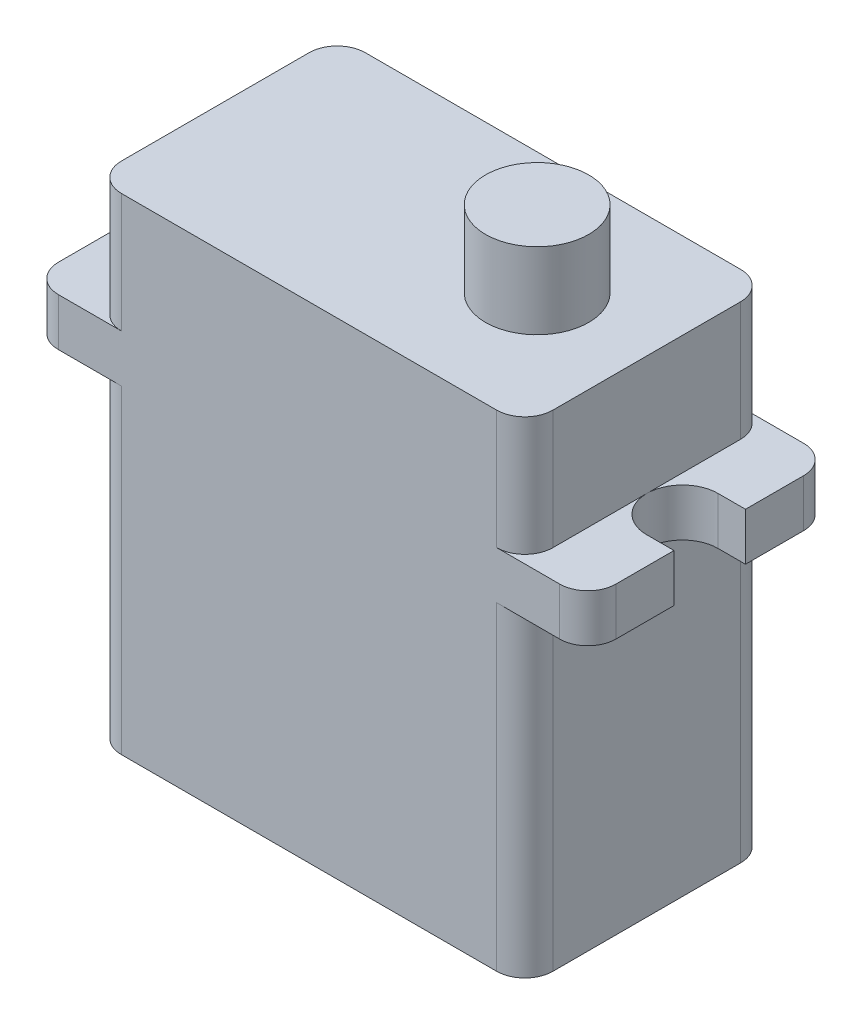
SolidWorks part; units mm, degrees
ref_plane "Front Plane" through (0, 0, 0) normal (0, 0, 1) x (1, 0, 0)
ref_plane "Top Plane" through (0, 0, 0) normal (0, 1, 0) x (1, 0, 0)
ref_plane "Right Plane" through (0, 0, 0) normal (1, 0, 0) x (0, 0, -1)
sketch "Sketch2" plane through (0, 0, 0) normal (0, 1, 0) x (1, 0, 0)
  line L1 (1.5, 0) -> (21.5, 0)
  line L2 (0, -1.5) -> (0, -11.5)
  line L3 (1.5, -13) -> (21.5, -13)
  line L4 (23, -1.5) -> (23, -11.5)
  arc A0 (21.5, -13) -> (23, -11.5) centre (21.5, -11.5) ccw
  arc A1 (1.5, -13) -> (0, -11.5) centre (1.5, -11.5) cw
  arc A2 (0, -1.5) -> (1.5, 0) centre (1.5, -1.5) cw
  arc A3 (23, -1.5) -> (21.5, 0) centre (21.5, -1.5) ccw
  point P7 (23, -13)
  point P12 (0, 0)
  point P15 (23, 0)
  dimension "D3" = 1.5
  dimension "D1" = 23
  dimension "D2" = 13
extrude "Boss-Extrude1" add sketch "Sketch2" along normal blind 17.018 contours L2 A1 L3 A0 L4 A3 L1 A2
sketch "Sketch3" plane through (0, 17.018, 0) normal (0, 1, 0) x (1, 0, 0)
  line L0 (1.5, -13) -> (21.5, -13) construction
  line L1 (-1.859, 0) -> (24.859, 0)
  line L2 (-3.359, -1.5) -> (-3.359, -11.5)
  line L3 (-1.859, -13) -> (24.859, -13)
  line L4 (26.359, -1.5) -> (26.359, -11.5)
  line L5 (1.5, 0) -> (21.5, 0) construction
  line L6 (23, -1.5) -> (23, -11.5) construction
  line L7 (24.905, -4.595) -> (26.359, -4.595)
  line L11 (1.5, 0) -> (21.5, 0) construction
  line L12 (24.905, -8.405) -> (26.359, -8.405)
  line L13 (0, -1.5) -> (0, -11.5) construction
  line L14 (-1.905, -4.595) -> (-3.359, -4.595)
  line L15 (-1.905, -8.405) -> (-3.359, -8.405)
  circle A1 centre (-1.905, -6.5) radius 1.905
  circle A3 centre (24.905, -6.5) radius 1.905
  arc A4 (24.859, -13) -> (26.359, -11.5) centre (24.859, -11.5) ccw
  arc A5 (26.359, -1.5) -> (24.859, 0) centre (24.859, -1.5) ccw
  arc A6 (-1.859, -13) -> (-3.359, -11.5) centre (-1.859, -11.5) cw
  arc A7 (-3.359, -1.5) -> (-1.859, 0) centre (-1.859, -1.5) cw
  point P13 (26.359, -6.5)
  point P21 (11.5, 0)
  point P28 (26.359, 0)
  point P33 (-3.359, 0)
  point P34 (11.5, 0)
  point P35 (11.5, -13)
  arc M13 (1.5, 0) -> (0, -1.5) centre (1.5, -1.5) ccw
  line M14 (0, -1.5) -> (0, -11.5)
  arc M15 (0, -11.5) -> (1.5, -13) centre (1.5, -11.5) ccw
  line M16 (1.5, -13) -> (21.5, -13)
  arc M17 (21.5, -13) -> (23, -11.5) centre (21.5, -11.5) ccw
  line M18 (23, -11.5) -> (23, -1.5)
  arc M19 (23, -1.5) -> (21.5, 0) centre (21.5, -1.5) ccw
  line M20 (21.5, 0) -> (1.5, 0)
  dimension "D3" = 1.5
  dimension "D2" = 3.81
  dimension "D1" = 29.718
extrude "Boss-Extrude2" add sketch "Sketch3" along normal blind 2.54 contours M20 M13 M14 M15 M16 M17 M18 M19 | A6 L3 A1 L15 L2 M15 M14 | A7 L2 L14 A1 L1 M14 M13 | L3 A4 L4 L12 A3 M18 M17 | L4 A5 L1 A3 L7 M19 M18 region at (-1.5192, 17.018, 2.4283) region at (11.5, 17.018, 6.5) region at (24.5192, 17.018, 2.4283) region at (-1.5192, 17.018, 10.5717) region at (24.5192, 17.018, 10.5717)
sketch "Sketch4" plane through (0, 19.558, 0) normal (0, 1, 0) x (1, 0, 0)
  line L0 (1.5, 0) -> (21.5, 0)
  line L1 (23, -1.5) -> (23, -11.5)
  line L2 (21.5, -13) -> (1.5, -13)
  line L4 (0, -11.5) -> (0, -1.5)
  arc A0 (21.5, -13) -> (23, -11.5) centre (21.5, -11.5) ccw
  arc A1 (21.5, 0) -> (23, -1.5) centre (21.5, -1.5) cw
  arc A2 (0, -11.5) -> (1.5, -13) centre (1.5, -11.5) ccw
  arc A3 (0, -1.5) -> (1.5, 0) centre (1.5, -1.5) cw
  circle A4 centre (17.158, -6.5) radius 2.75
  point P12 (23, -13)
  point P15 (23, 0)
  point P18 (0, -13)
  point P21 (0, 0)
  point P24 (16.9714, -6.4529)
  point P25 (0, 0)
  point P26 (18.0842, -6.5)
  point P28 (17.158, -4.595)
  point P29 (17.158, -4.595)
  point P31 (17.158, -5.5232)
  point P33 (0, 0)
  point P34 (0, 0)
  dimension "D1" = 1.5
  dimension "D2" = 5.5
  dimension "D3" = 5.842
extrude "Boss-Extrude3" add sketch "Sketch4" along normal blind 6.35 contours L4 A3 L0 A1 L1 A0 L2 A2
extrude "Boss-Extrude4" add sketch "Sketch4<4>" along normal blind 10.414 contours A4 region at (17.158, 19.558, 6.5)
sketch "Sketch4<4>" plane through (0, 19.558, 0) normal (0, 1, 0) x (1, 0, 0) same geometry as "Sketch4"
